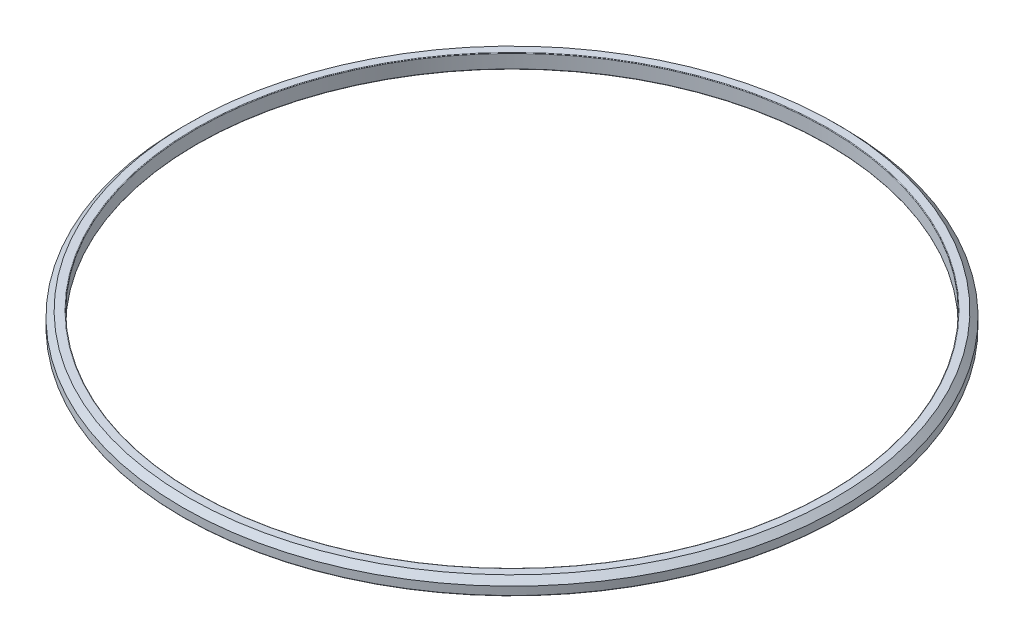
SolidWorks part; units mm, degrees
material "PETG"
ref_plane "Front Plane" through (0, 0, 0) normal (0, 0, 1) x (1, 0, 0)
ref_plane "Top Plane" through (0, 0, 0) normal (0, 1, 0) x (1, 0, 0)
ref_plane "Right Plane" through (0, 0, 0) normal (1, 0, 0) x (0, 0, -1)
sketch "Sketch1" plane through (0, 0, 0) normal (0, 1, 0) x (1, 0, 0)
  circle A0 centre (0, 0) radius 57.2125
  circle A1 centre (0, 0) radius 54.7875
  dimension "Ring OD" = 114.425
  dimension "Ring ID" = 109.575
extrude "Boss-Extrude1" add sketch "Sketch1" along normal blind 2.5
chamfer "Chamfer1" distance 1 angle 45 1 edges at (0, 2.5, 57.2125)
fillet "Fillet1" radius 0.1 3 edges at (0, 2.5, 54.7875) (0, 0, 54.7875) (0, 0, 57.2125)
equation "\"tol_dia_id_intfc\"= 0.0500mm ' For hole diameters - Interference fit"
equation "\"tol_dia_id_slip\"= 0.0750mm ' For hole diameters - Slip fit"
equation "\"tol_dia_id_clear\"= 0.1000mm ' For hole diameters - Clearance fit"
equation "\"tol_dia_od_intfc\"= 0.0500mm ' For shaft diameters - Interference fit"
equation "\"tol_dia_od_slip\"= 0.0750mm ' For shaft diameters - Slip fit"
equation "\"tol_dia_od_clear\"= 0.1000mm ' For shaft diameters - Clearance fit"
equation "\"tol_general_intfc\"= 0.0250mm ' For general parts (Horiz) - Interference fit"
equation "\"tol_general_slip\"= 0.0375mm ' For general parts (Horiz) - Slip fit"
equation "\"tol_general_clear\"= 0.0500mm ' For general parts (Horiz) - Clearance fit"
equation "\"tol_layer_intfc\"= 0.0250mm ' For all parts (Vert) - Interference fit"
equation "\"tol_layer_slip\"= 0.0375mm ' For all parts (Vert) - Slip fit"
equation "\"tol_layer_clear\"= 0.0500mm ' For all parts (Vert) - Clearance fit"
equation "\"tol_corner_rad\"= 0.100mm ' For corners that fit into other parts"
equation "\"Ring OD@Sketch1\"= 114.50mm - \"tol_dia_od_slip\""
equation "\"Ring ID@Sketch1\" = 114.5 - ( 2.5 * 2 ) + \"tol_dia_id_slip\""
equation "\"D1@Fillet1\"=\"tol_corner_rad\""
